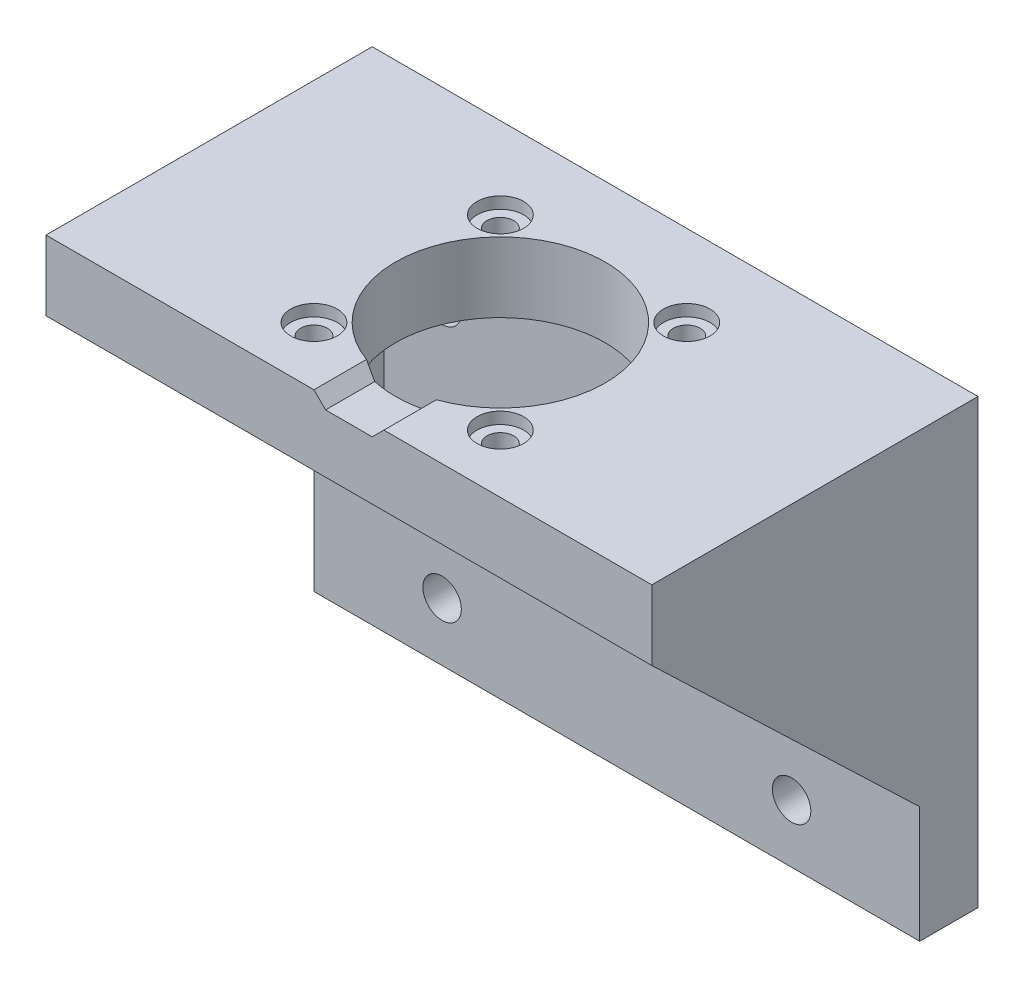
SolidWorks part; units mm, degrees
ref_plane "Front Plane" through (0, 0, 0) normal (0, 0, 1) x (1, 0, 0)
ref_plane "Top Plane" through (0, 0, 0) normal (0, 1, 0) x (1, 0, 0)
ref_plane "Right Plane" through (0, 0, 0) normal (1, 0, 0) x (0, 0, -1)
sketch "Sketch1" plane through (0, 0, 0) normal (0, 0, 1) x (1, 0, 0)
  line L1 (-83.9142, 121.7372) -> (-31.9142, 121.7372)
  line L2 (-83.9142, 121.7372) -> (-83.9142, 83.7372)
  line L3 (-83.9142, 83.7372) -> (-31.9142, 83.7372)
  line L4 (-31.9142, 121.7372) -> (-31.9142, 83.7372)
  dimension "D1" = 52
  dimension "D2" = 38
extrude "Boss-Extrude1" add sketch "Sketch1" along normal blind 5
sketch "Sketch2" plane through (0, 0, 5) normal (0, 0, 1) x (1, 0, 0)
  line L0 (-31.9142, 83.7372) -> (-31.9142, 121.7372) construction
  line L1 (-83.9142, 121.7372) -> (-31.9142, 121.7372)
  line L2 (-83.9142, 121.7372) -> (-83.9142, 115.7372)
  line L3 (-83.9142, 115.7372) -> (-31.9142, 115.7372)
  line L4 (-31.9142, 121.7372) -> (-31.9142, 115.7372)
  dimension "D1" = 6
extrude "Boss-Extrude2" add sketch "Sketch2" along normal blind 23
sketch "Sketch3" plane through (0, 121.7372, 0) normal (0, 1, 0) x (1, 0, 0)
  circle A0 centre (-57.9141, -15.0001) radius 9
  dimension "D1" = 18
extrude "Cut-Extrude1" cut sketch "Sketch3" against normal up to surface (6 mm away) up to face at (-57.9142, 115.7372, 16.5)
sketch "Sketch4" plane through (0, 115.7372, 0) normal (0, -1, 0) x (1, 0, 0)
  circle A0 centre (-65.9141, 23.0001) radius 1.15
  circle A1 centre (-49.9141, 23.0001) radius 1.15
  circle A2 centre (-49.9141, 7.0001) radius 1.15
  circle A3 centre (-65.9141, 7.0001) radius 1.15
  dimension "D1" = 2.3
  dimension "D2" = 2.3
  dimension "D3" = 2.3
  dimension "D4" = 2.3
extrude "Cut-Extrude2" cut sketch "Sketch4" against normal up to surface (6 mm away) up to face at (-57.9141, 121.7372, 24.0001)
sketch "Sketch5" plane through (0, 0, 5) normal (0, 0, 1) x (1, 0, 0)
  line L0 (-83.9142, 115.7372) -> (-31.9142, 115.7372) construction
  line L1 (-83.9142, 83.7372) -> (-77.9142, 83.7372)
  line L2 (-83.9142, 83.7372) -> (-83.9142, 115.7372)
  line L3 (-83.9142, 115.7372) -> (-77.9142, 115.7372)
  line L4 (-77.9142, 83.7372) -> (-77.9142, 115.7372)
  line L6 (-31.9142, 83.7372) -> (-37.9142, 83.7372)
  line L7 (-31.9142, 83.7372) -> (-31.9142, 115.7372)
  line L8 (-31.9142, 115.7372) -> (-37.9142, 115.7372)
  line L9 (-37.9142, 83.7372) -> (-37.9142, 115.7372)
  dimension "D1" = 6
  dimension "D2" = 6
extrude "Boss-Extrude3" add sketch "Sketch5" along normal up to surface (23 mm away) up to face at (-57.9142, 118.7372, 28)
sketch "Sketch6" plane through (-83.9142, 0, 0) normal (-1, 0, 0) x (0, 0, 1)
  line L0 (5, 83.7372) -> (5, 93.7372)
  line L1 (28, 83.7372) -> (0, 83.7372) construction
  line L2 (5, 93.7372) -> (28, 115.7372)
  line L3 (28, 121.7372) -> (28, 83.7372) construction
  line L4 (28, 115.7372) -> (34.8002, 115.7372)
  line L5 (34.8002, 115.7372) -> (34.8002, 79.151)
  line L6 (34.8002, 79.151) -> (5, 79.151)
  line L7 (5, 79.151) -> (5, 83.7372)
  line L8 (28, 121.7372) -> (0, 121.7372) construction
  line L9 (0, 121.7372) -> (0, 83.7372) construction
  dimension "D1" = 6
  dimension "D2" = 10
  dimension "D3" = 5
extrude "Cut-Extrude3" cut sketch "Sketch6" against normal through all
sketch "Sketch7" plane through (0, 0, 5) normal (0, 0, 1) x (1, 0, 0)
  line L0 (-77.9142, 115.7372) -> (-37.9142, 115.7372) construction
  line L1 (-77.9142, 115.7372) -> (-77.9142, 93.7372) construction
  line L2 (-37.9142, 93.7372) -> (-37.9142, 115.7372) construction
  line L3 (-83.9142, 83.7372) -> (-31.9142, 83.7372) construction
  circle A0 centre (-42.9142, 110.7372) radius 1.65
  circle A1 centre (-42.9142, 88.7372) radius 1.65
  circle A2 centre (-72.9142, 110.7372) radius 1.65
  circle A3 centre (-72.9142, 88.7372) radius 1.65
  dimension "D1" = 3.3
  dimension "D2" = 3.3
  dimension "D3" = 3.3
  dimension "D4" = 3.3
  dimension "D5" = 5
  dimension "D6" = 5
  dimension "D7" = 5
  dimension "D8" = 5
  dimension "D9" = 5
  dimension "D10" = 5
  dimension "D11" = 5
  dimension "D12" = 5
extrude "Cut-Extrude4" cut sketch "Sketch7" against normal blind 5
sketch "Sketch8" plane through (0, 0, 5) normal (0, 0, 1) x (1, 0, 0)
  line L0 (-37.9142, 93.7372) -> (-37.9142, 115.7372) construction
  line L1 (-77.9142, 115.7372) -> (-77.9142, 93.7372) construction
  line L2 (-77.9142, 115.7372) -> (-37.9142, 115.7372) construction
  circle A0 centre (-72.9142, 99.7372) radius 1.65
  circle A1 centre (-42.9142, 99.7372) radius 1.65
  dimension "D1" = 3.3
  dimension "D2" = 3.3
  dimension "D3" = 5
  dimension "D4" = 5
  dimension "D5" = 16
  dimension "D6" = 16
extrude "Cut-Extrude5" cut sketch "Sketch8" against normal blind 5
sketch "Sketch9" plane through (0, 121.7372, 0) normal (0, 1, 0) x (1, 0, 0)
  line L0 (-31.9142, -28) -> (-83.9142, -28) construction
  line L1 (-54.9142, -28) -> (-60.9142, -28)
  line L2 (-54.9142, -28) -> (-54.9142, -23.1853)
  line L3 (-54.9142, -23.1853) -> (-60.9142, -23.1853)
  line L4 (-60.9142, -28) -> (-60.9142, -23.1853)
  line L5 (-31.9142, -28) -> (-31.9142, 0) construction
  line L6 (-83.9142, -28) -> (-83.9142, 0) construction
  dimension "D1" = 23
  dimension "D2" = 23
extrude "Cut-Extrude6" cut sketch "Sketch9" against normal blind 1
chamfer "Chamfer1" distance 1 angle 45 2 edges at (-60.9142, 120.7372, 25.7427) (-54.9142, 120.7372, 25.7427)
sketch "Sketch10" plane through (0, 121.7372, 0) normal (0, 1, 0) x (1, 0, 0)
  circle A0 centre (-65.9141, -7.0001) radius 2
  circle A1 centre (-49.9141, -7.0001) radius 2
  circle A2 centre (-49.9141, -23.0001) radius 2
  circle A3 centre (-65.9141, -23.0001) radius 2
  dimension "D1" = 4
  dimension "D2" = 4
  dimension "D3" = 4
  dimension "D4" = 4
extrude "Cut-Extrude7" cut sketch "Sketch10" against normal blind 1
